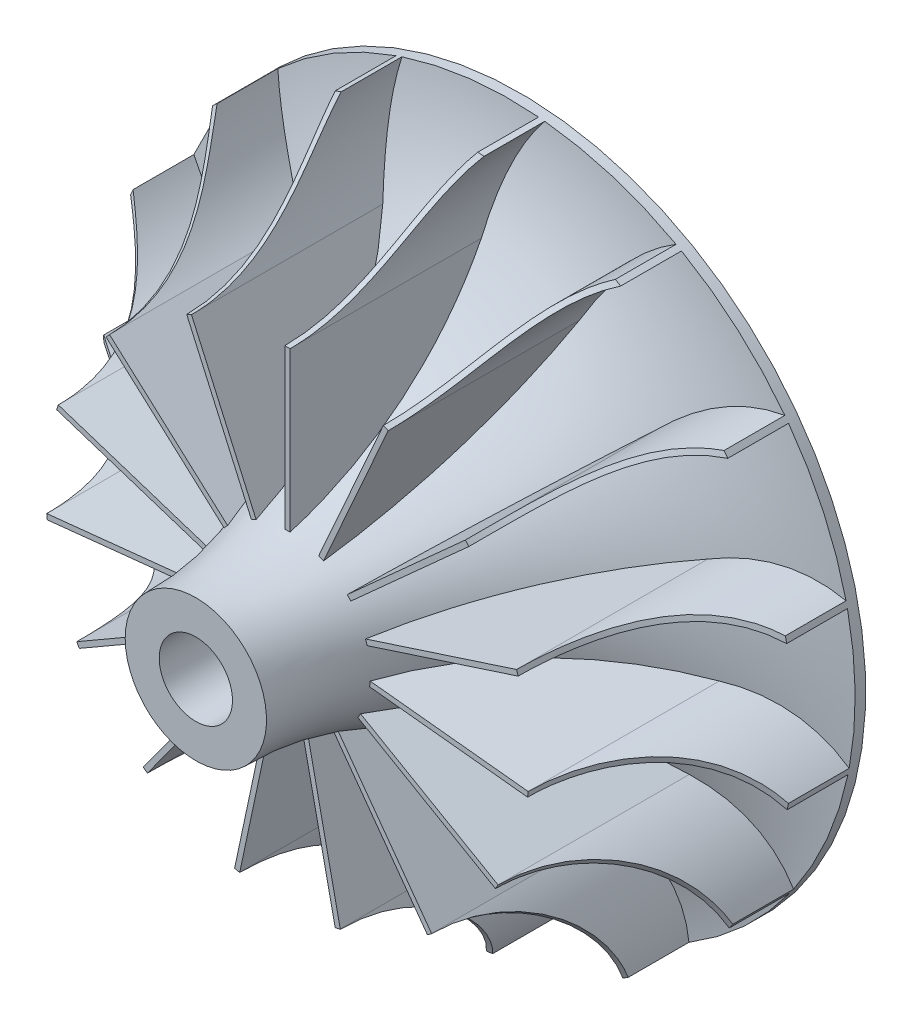
SolidWorks part; units mm, degrees
material "Ti-10V-2Fe-3Al Solution Treated Bar (SS)"
ref_plane "Front Plane" through (0, 0, 0) normal (0, 0, 1) x (1, 0, 0)
ref_plane "Top Plane" through (0, 0, 0) normal (0, 1, 0) x (1, 0, 0)
ref_plane "Right Plane" through (0, 0, 0) normal (1, 0, 0) x (0, 0, -1)
sketch "Sketch1" plane through (0, 0, 0) normal (0, 1, 0) x (1, 0, 0)
  line L0 (0, 31) -> (-33, 31)
  line L1 (-33, 31) -> (-33, 30)
  line L2 (0, 0) -> (-6.75, 0)
  line L3 (0, 31) -> (0, 0) construction
  line L4 (0, 31) -> (0, 0)
  arc A0 (-33, 30) -> (-6.75, 0) centre (-36.4801, 0.4705) cw
  point P0 (0, 31)
revolve "Revolve1" add sketch "Sketch1" angle 360 about L3
sketch "Sketch2" plane through (0, 0, 0) normal (0, 1, 0) x (1, 0, 0)
  line L0 (0.25, 8.75) -> (-0.25, 8.75)
  line L2 (-0.25, 8.75) -> (-0.25, 30)
  line L3 (-0.25, 30) -> (0.25, 30)
  line L4 (-33, 30) -> (33, 30) construction
  line L5 (0.25, 8.75) -> (0.25, 30)
  point P0 (0, 8.75)
  point P11 (0, 30)
  point P12 (0, 8.75)
sketch "Sketch3" plane through (0, 0, 0) normal (0, 0, 1) x (1, 0, 0)
  line L0 (0, 0) -> (0, 23.1)
  arc A0 (0, 23.1) -> (11.4248, 38.178) centre (14.5944, 23.909) cw
  dimension "D1" = 23.1
  dimension "D2" = 39.8508
sweep "Sweep1" add profiles "Sketch2" path "Sketch3"
sketch "Sketch4" plane through (0, 0, 0) normal (0, 1, 0) x (1, 0, 0)
  circle A0 centre (40.1, 8.75) radius 17
  point P0 (40.1, 8.75)
sketch "Sketch5" plane through (0, 0, 0) normal (0, 0, 1) x (1, 0, 0)
  circle A0 centre (0, 0) radius 40.1
sketch "Sketch6" plane through (0, 0, 0) normal (0, 0, 1) x (1, 0, 0)
  circle A0 centre (0, 0) radius 3.5
pattern_circular "CirPattern5" count 15 over 360 about axis through (0, 0, -30) along (0, 0, -1) of "Sweep1"
sweep "Cut-Sweep1" cut profiles "Sketch4" path "Sketch5"
extrude "Cut-Extrude6" cut sketch "Sketch6" against normal blind 50
sketch "Sketch14" plane through (0, 0, 0) normal (0, 0, 1) x (1, 0, 0)
  circle A0 centre (0, 0) radius 45.3404
  circle A1 centre (0, 0) radius 33
extrude "Cut-Extrude7" cut sketch "Sketch14" against normal blind 50
ref_axis "Axis1" through (0, 0, -31) along (0, 0, 1)
